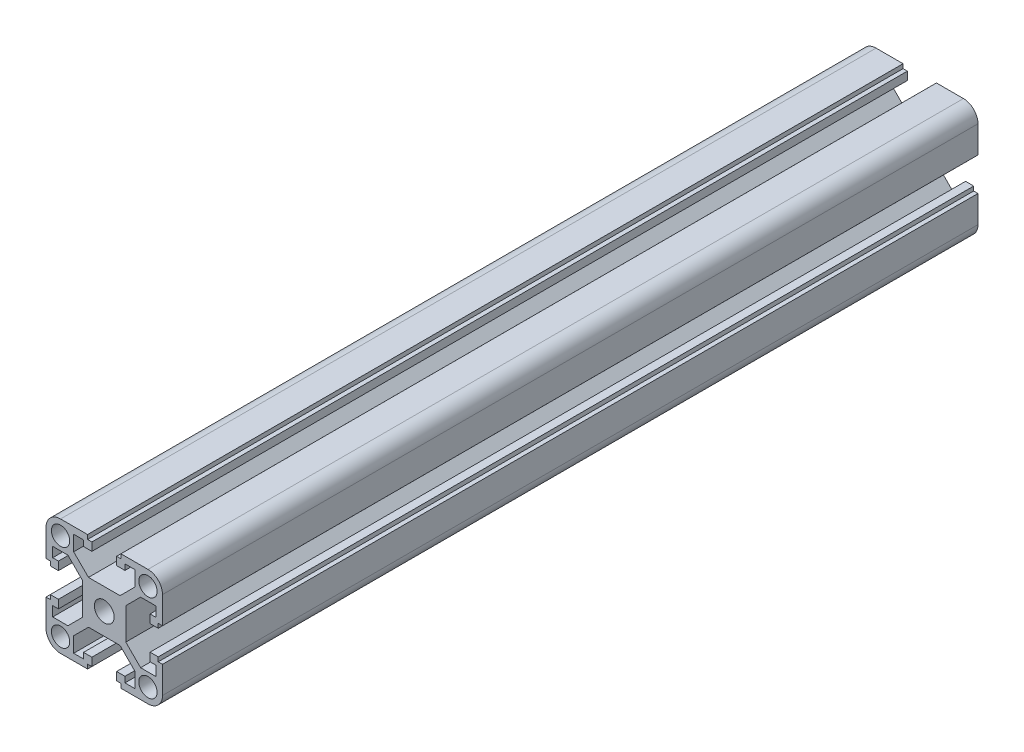
SolidWorks part; units mm, degrees
material "АД1 ГОСТ 4784-97"
ref_plane "Спереди" through (0, 0, 0) normal (0, 0, 1) x (1, 0, 0)
ref_plane "Сверху" through (0, 0, 0) normal (0, 1, 0) x (1, 0, 0)
ref_plane "Справа" through (0, 0, 0) normal (1, 0, 0) x (0, 0, -1)
ref_axis "ОсьX" through (-88.99, 0, 0) along (1, 0, 0)
ref_axis "ОсьZ" through (0, 55, 0) along (0, -1, 0)
ref_axis "ОсьY" through (0, 0, -88.99) along (0, 0, 1)
sketch "Эскиз1" plane through (0, 0, 0) normal (0, 0, 1) x (1, 0, 0)
  line L0 (-15, 20) -> (-5.7274, 20)
  line L1 (-5.7274, 20) -> (-5.7274, 18.5304)
  line L2 (-5.7274, 18.5304) -> (-4.25, 18.5304)
  line L3 (-4.25, 18.5304) -> (-4.25, 15.732)
  line L4 (-4.25, 15.732) -> (-7.1118, 15.732)
  line L5 (-7.1118, 15.732) -> (-7.1118, 17.7)
  line L6 (-7.1118, 17.7) -> (-10.5, 17.7)
  line L7 (-10.5, 17.7) -> (-10.5, 12.4799)
  line L8 (-10.5, 12.4799) -> (-5.4201, 7.4)
  line L9 (-20, 15) -> (-20, 5.7274)
  line L10 (0, 0) -> (0, 8.4096) construction
  line L11 (-15, 15) -> (0, 0) construction
  line L12 (10.5, 12.4799) -> (5.4201, 7.4)
  line L13 (10.5, 17.7) -> (10.5, 12.4799)
  line L14 (7.1118, 17.7) -> (10.5, 17.7)
  line L15 (7.1118, 15.732) -> (7.1118, 17.7)
  line L16 (4.25, 15.732) -> (7.1118, 15.732)
  line L17 (4.25, 18.5304) -> (4.25, 15.732)
  line L18 (5.7274, 18.5304) -> (4.25, 18.5304)
  line L19 (5.7274, 20) -> (5.7274, 18.5304)
  line L20 (15, 20) -> (5.7274, 20)
  line L21 (-5.4201, 7.4) -> (5.4201, 7.4)
  line L22 (-8.8445, 0) -> (0, 0) construction
  line L23 (-12.4799, 10.5) -> (-7.4, 5.4201)
  line L24 (-17.7, 10.5) -> (-12.4799, 10.5)
  line L25 (-17.7, 7.1118) -> (-17.7, 10.5)
  line L26 (-15.732, 7.1118) -> (-17.7, 7.1118)
  line L27 (-15.732, 4.25) -> (-15.732, 7.1118)
  line L28 (-18.5304, 4.25) -> (-15.732, 4.25)
  line L29 (-18.5304, 5.7274) -> (-18.5304, 4.25)
  line L30 (-20, 5.7274) -> (-18.5304, 5.7274)
  line L31 (18.5304, 5.7274) -> (18.5304, 4.25)
  line L32 (18.5304, 4.25) -> (15.732, 4.25)
  line L33 (15.732, 4.25) -> (15.732, 7.1118)
  line L34 (15.732, 7.1118) -> (17.7, 7.1118)
  line L35 (12.4799, 10.5) -> (7.4, 5.4201)
  line L36 (17.7, 10.5) -> (12.4799, 10.5)
  line L37 (17.7, 7.1118) -> (17.7, 10.5)
  line L38 (20, 5.7274) -> (18.5304, 5.7274)
  line L39 (20, 15) -> (20, 5.7274)
  line L40 (20, -15) -> (20, -5.7274)
  line L41 (20, -5.7274) -> (18.5304, -5.7274)
  line L42 (17.7, -7.1118) -> (17.7, -10.5)
  line L43 (17.7, -10.5) -> (12.4799, -10.5)
  line L44 (12.4799, -10.5) -> (7.4, -5.4201)
  line L45 (15.732, -7.1118) -> (17.7, -7.1118)
  line L46 (15.732, -4.25) -> (15.732, -7.1118)
  line L47 (18.5304, -4.25) -> (15.732, -4.25)
  line L48 (18.5304, -5.7274) -> (18.5304, -4.25)
  line L49 (-20, -5.7274) -> (-18.5304, -5.7274)
  line L50 (-18.5304, -5.7274) -> (-18.5304, -4.25)
  line L51 (-18.5304, -4.25) -> (-15.732, -4.25)
  line L52 (-15.732, -4.25) -> (-15.732, -7.1118)
  line L53 (-15.732, -7.1118) -> (-17.7, -7.1118)
  line L54 (-17.7, -7.1118) -> (-17.7, -10.5)
  line L55 (-17.7, -10.5) -> (-12.4799, -10.5)
  line L56 (-12.4799, -10.5) -> (-7.4, -5.4201)
  line L57 (-5.4201, -7.4) -> (5.4201, -7.4)
  line L58 (15, -20) -> (5.7274, -20)
  line L59 (5.7274, -20) -> (5.7274, -18.5304)
  line L60 (5.7274, -18.5304) -> (4.25, -18.5304)
  line L61 (4.25, -18.5304) -> (4.25, -15.732)
  line L62 (4.25, -15.732) -> (7.1118, -15.732)
  line L63 (7.1118, -15.732) -> (7.1118, -17.7)
  line L64 (7.1118, -17.7) -> (10.5, -17.7)
  line L65 (10.5, -17.7) -> (10.5, -12.4799)
  line L66 (10.5, -12.4799) -> (5.4201, -7.4)
  line L67 (-20, -15) -> (-20, -5.7274)
  line L68 (-10.5, -12.4799) -> (-5.4201, -7.4)
  line L69 (-10.5, -17.7) -> (-10.5, -12.4799)
  line L70 (-7.1118, -17.7) -> (-10.5, -17.7)
  line L71 (-7.1118, -15.732) -> (-7.1118, -17.7)
  line L72 (-4.25, -15.732) -> (-7.1118, -15.732)
  line L73 (-4.25, -18.5304) -> (-4.25, -15.732)
  line L74 (-5.7274, -18.5304) -> (-4.25, -18.5304)
  line L75 (-5.7274, -20) -> (-5.7274, -18.5304)
  line L76 (-15, -20) -> (-5.7274, -20)
  line L77 (-7.4, 5.4201) -> (-7.4, -5.4201)
  line L78 (7.4, 5.4201) -> (7.4, -5.4201)
  circle A0 centre (0, 0) radius 3.4
  circle A1 centre (-15, 15) radius 3.15
  arc A2 (-15, 20) -> (-20, 15) centre (-15, 15) ccw
  arc A3 (15, 20) -> (20, 15) centre (15, 15) cw
  circle A4 centre (15, 15) radius 3.15
  circle A5 centre (15, -15) radius 3.15
  arc A6 (15, -20) -> (20, -15) centre (15, -15) ccw
  arc A7 (-15, -20) -> (-20, -15) centre (-15, -15) cw
  circle A8 centre (-15, -15) radius 3.15
  dimension "D1" = 6.8
  dimension "D2" = 6.3
  dimension "D3" = 40
  dimension "D8" = 30
  dimension "D4" = 2.3
  dimension "D5" = 1.35
  dimension "D6" = 21
  dimension "D7" = 8.5
  dimension "D9" = 45
  dimension "D10" = 2.8
  dimension "D11" = 4
  dimension "D13" = 40
extrude "Бобышка-Вытянуть1" add sketch "Эскиз1" along normal mid plane 280
